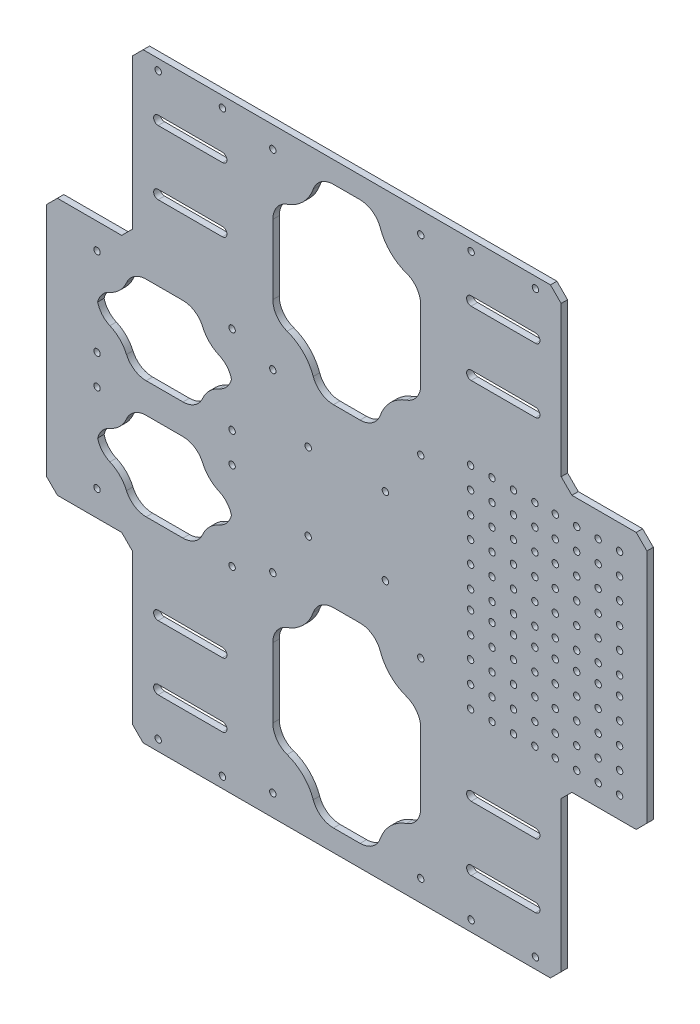
SolidWorks part; units mm, degrees
ref_plane "前视基准面" through (0, 0, 0) normal (0, 0, 1) x (1, 0, 0)
ref_plane "上视基准面" through (0, 0, 0) normal (0, 1, 0) x (1, 0, 0)
ref_plane "右视基准面" through (0, 0, 0) normal (1, 0, 0) x (0, 0, -1)
other "Configuration Table"
sketch "草图1" plane through (0, 0, 0) normal (0, 0, 1) x (1, 0, 0)
  line L0 (-100, -140) -> (-100, -60)
  line L1 (-100, 140) -> (100, 140)
  line L2 (-140, 60) -> (-140, -60)
  line L3 (-100, -140) -> (100, -140)
  line L4 (140, 60) -> (140, -60)
  line L5 (-100, 60) -> (100, -60) construction
  line L6 (-100, -60) -> (100, 60) construction
  line L7 (-100, -60) -> (-140, -60)
  line L8 (140, 60) -> (100, 60)
  line L9 (-140, 60) -> (-100, 60)
  line L10 (-100, 60) -> (-100, 140)
  line L11 (100, 60) -> (100, 140)
  line L12 (100, -140) -> (100, -60)
  line L13 (100, -60) -> (140, -60)
  line L14 (-88, -85) -> (-58, -85) construction
  line L15 (-88, -82.9) -> (-58, -82.9)
  line L16 (-88, -87.1) -> (-58, -87.1)
  line L17 (-88, -115) -> (-58, -115) construction
  line L18 (-88, -112.9) -> (-58, -112.9)
  line L19 (-88, -117.1) -> (-58, -117.1)
  line L20 (-140, 0) -> (140, 0) construction
  line L21 (0, 140) -> (0, -140) construction
  line L22 (88, -115) -> (58, -115) construction
  line L23 (88, -112.9) -> (58, -112.9)
  line L24 (88, -117.1) -> (58, -117.1)
  line L25 (88, -85) -> (58, -85) construction
  line L26 (88, -82.9) -> (58, -82.9)
  line L27 (88, -87.1) -> (58, -87.1)
  line L28 (88, 115) -> (58, 115) construction
  line L29 (88, 112.9) -> (58, 112.9)
  line L30 (88, 117.1) -> (58, 117.1)
  line L31 (88, 85) -> (58, 85) construction
  line L32 (88, 82.9) -> (58, 82.9)
  line L33 (88, 87.1) -> (58, 87.1)
  line L34 (-88, 115) -> (-58, 115) construction
  line L35 (-88, 112.9) -> (-58, 112.9)
  line L36 (-88, 117.1) -> (-58, 117.1)
  line L37 (-88, 85) -> (-58, 85) construction
  line L38 (-88, 82.9) -> (-58, 82.9)
  line L39 (-88, 87.1) -> (-58, 87.1)
  arc A0 (-88, -82.9) -> (-88, -87.1) centre (-88, -85) ccw
  arc A1 (-58, -87.1) -> (-58, -82.9) centre (-58, -85) ccw
  arc A2 (-88, -112.9) -> (-88, -117.1) centre (-88, -115) ccw
  arc A3 (-58, -117.1) -> (-58, -112.9) centre (-58, -115) ccw
  arc A4 (88, -112.9) -> (88, -117.1) centre (88, -115) cw
  arc A5 (58, -117.1) -> (58, -112.9) centre (58, -115) cw
  arc A6 (88, -82.9) -> (88, -87.1) centre (88, -85) cw
  arc A7 (58, -87.1) -> (58, -82.9) centre (58, -85) cw
  arc A8 (88, 112.9) -> (88, 117.1) centre (88, 115) ccw
  arc A9 (58, 117.1) -> (58, 112.9) centre (58, 115) ccw
  arc A10 (88, 82.9) -> (88, 87.1) centre (88, 85) ccw
  arc A11 (58, 87.1) -> (58, 82.9) centre (58, 85) ccw
  arc A12 (-88, 112.9) -> (-88, 117.1) centre (-88, 115) cw
  arc A13 (-58, 117.1) -> (-58, 112.9) centre (-58, 115) cw
  arc A14 (-88, 82.9) -> (-88, 87.1) centre (-88, 85) cw
  arc A15 (-58, 87.1) -> (-58, 82.9) centre (-58, 85) cw
  circle A16 centre (-34.5, -130) radius 1.5
  circle A17 centre (-34.5, -41) radius 1.5
  circle A18 centre (34.5, -130) radius 1.5
  circle A19 centre (34.5, -41) radius 1.5
  circle A22 centre (-34.5, 130) radius 1.5
  circle A23 centre (34.5, 130) radius 1.5
  circle A24 centre (34.5, 41) radius 1.5
  circle A25 centre (-34.5, 41) radius 1.5
  point P0 (0, 0)
  point P1 (0, 0)
  point P6 (-73, -85)
  point P23 (-73, -115)
  point P35 (73, -115)
  point P42 (73, -85)
  point P49 (73, 115)
  point P56 (73, 85)
  point P63 (-73, 115)
  point P70 (-73, 85)
  dimension "D3" = 40
  dimension "D12" = 2.1
  dimension "D13" = 2.1
  dimension "D16" = 34.5
  dimension "D17" = 89
  dimension "D20" = 3
  dimension "D21" = 3
  dimension "D1" = 280
  dimension "D2" = 40
  dimension "D4" = 280
  dimension "D5" = 80
  dimension "D6" = 80
  dimension "D7" = 80
  dimension "D8" = 30
  dimension "D9" = 25
  dimension "D10" = 30
  dimension "D11" = 30
  dimension "D14" = 12
  dimension "D15" = 12
  dimension "D18" = 10
  dimension "D19" = 34.5
extrude "凸台-拉伸1" add sketch "草图1" along normal blind 3
chamfer "倒角1" distance 5 angle 45 12 edges at (100, 60, 1.5) (100, -60, 1.5) (-100, -60, 1.5) (-100, 60, 1.5) (140, 60, 1.5) (140, -60, 1.5) (-140, -60, 1.5) (-140, 60, 1.5) (100, 140, 1.5) (-100, 140, 1.5) (-100, -140, 1.5) (100, -140, 1.5)
sketch "草图3" plane through (0, 0, 3) normal (0, 0, 1) x (1, 0, 0)
  line L0 (-140, 0) -> (140, 0) construction
  line L1 (-140, 55) -> (-140, -55) construction
  line L2 (140, -55) -> (140, 55) construction
  line L3 (0, 140) -> (0, -140) construction
  line L4 (95, 140) -> (-95, 140) construction
  line L5 (-95, -140) -> (95, -140) construction
  line L6 (-14.5, 130) -> (14.5, 130)
  line L11 (-18, 18) -> (18, -18) construction
  line L12 (-18, -18) -> (18, 18) construction
  line L17 (-34.5, 110) -> (-34.5, 61)
  line L18 (-14.5, 41) -> (14.5, 41)
  line L19 (34.5, 110) -> (34.5, 61)
  line L20 (-14.5, -41) -> (14.5, -41)
  line L21 (34.5, -110) -> (34.5, -61)
  line L22 (-14.5, -130) -> (14.5, -130)
  line L23 (-34.5, -110) -> (-34.5, -61)
  line L24 (-101.5, -48) -> (-68.5, -48)
  line L26 (-116.5, -33) -> (-116.5, -22)
  line L30 (-101.5, -7) -> (-68.5, -7)
  line L31 (-53.5, -33) -> (-53.5, -22)
  line L33 (-101.5, 7) -> (-68.5, 7)
  line L34 (-103.9279, 15.1818) -> (-66.0721, 39.8182) construction
  line L36 (-116.5, 33) -> (-116.5, 22)
  line L37 (-103.9279, 39.8182) -> (-66.0721, 15.1818) construction
  line L38 (-101.5, 48) -> (-68.5, 48)
  line L41 (-53.5, 33) -> (-53.5, 22)
  circle A0 centre (-88, 135) radius 1.5
  circle A1 centre (-58, 135) radius 1.5
  circle A42 centre (58, 135) radius 1.5
  circle A43 centre (88, 135) radius 1.5
  circle A84 centre (88, -135) radius 1.5
  circle A85 centre (58, -135) radius 1.5
  circle A86 centre (-58, -135) radius 1.5
  circle A87 centre (-88, -135) radius 1.5
  circle A92 centre (-18, 18) radius 1.5
  circle A93 centre (18, 18) radius 1.5
  circle A94 centre (18, -18) radius 1.5
  circle A95 centre (-18, -18) radius 1.5
  arc A240 (-14.5, 41) -> (-34.5, 61) centre (-34.5, 41) ccw
  arc A241 (34.5, 61) -> (14.5, 41) centre (34.5, 41) ccw
  arc A242 (-34.5, 110) -> (-14.5, 130) centre (-34.5, 130) ccw
  arc A243 (14.5, 130) -> (34.5, 110) centre (34.5, 130) ccw
  arc A244 (34.5, -61) -> (14.5, -41) centre (34.5, -41) cw
  arc A245 (14.5, -130) -> (34.5, -110) centre (34.5, -130) cw
  arc A246 (-34.5, -110) -> (-14.5, -130) centre (-34.5, -130) cw
  arc A247 (-14.5, -41) -> (-34.5, -61) centre (-34.5, -41) cw
  circle A262 centre (-116.5, 48) radius 1.5
  circle A263 centre (-53.5, 48) radius 1.5
  circle A321 centre (-53.5, 7) radius 1.5
  circle A322 centre (-116.5, 7) radius 1.5
  arc A323 (-116.5, 33) -> (-101.5, 48) centre (-116.5, 48) ccw
  arc A324 (-68.5, 48) -> (-53.5, 33) centre (-53.5, 48) ccw
  arc A325 (-101.5, 7) -> (-116.5, 22) centre (-116.5, 7) ccw
  arc A326 (-53.5, 22) -> (-68.5, 7) centre (-53.5, 7) ccw
  circle A327 centre (-53.5, -7) radius 1.5
  circle A328 centre (-53.5, -48) radius 1.5
  circle A329 centre (-116.5, -48) radius 1.5
  circle A330 centre (-116.5, -7) radius 1.5
  arc A331 (-116.5, -33) -> (-101.5, -48) centre (-116.5, -48) cw
  arc A357 (-101.5, -7) -> (-116.5, -22) centre (-116.5, -7) cw
  arc A358 (-53.5, -22) -> (-68.5, -7) centre (-53.5, -7) cw
  arc A359 (-68.5, -48) -> (-53.5, -33) centre (-53.5, -48) cw
  point P2 (0, 0)
  point P29 (-85, 27.5)
  point P189 (0, 0)
  point P194 (0, 0)
  dimension "D1" = 55
  dimension "D4" = 63
  dimension "D5" = 41
extrude "切除-拉伸2" cut sketch "草图3" against normal blind 10
fillet "圆角1" radius 10 32 edges at (-34.5, -61, 1.5) (-14.5, -41, 1.5) (34.5, -61, 1.5) (14.5, -41, 1.5) (14.5, -130, 1.5) (34.5, -110, 1.5) (-14.5, -130, 1.5) (-34.5, -110, 1.5) (-34.5, 61, 1.5) (-14.5, 41, 1.5) (14.5, 41, 1.5) (34.5, 61, 1.5) (34.5, 110, 1.5) (14.5, 130, 1.5) (-34.5, 110, 1.5) (-14.5, 130, 1.5) (-68.5, -7, 1.5) (-101.5, -7, 1.5) (-116.5, -22, 1.5) (-116.5, -33, 1.5) (-101.5, -48, 1.5) (-68.5, -48, 1.5) (-53.5, -33, 1.5) (-53.5, -22, 1.5) (-53.5, 22, 1.5) (-53.5, 33, 1.5) (-68.5, 48, 1.5) (-68.5, 7, 1.5) (-101.5, 7, 1.5) (-116.5, 22, 1.5) (-116.5, 33, 1.5) (-101.5, 48, 1.5)
sketch "草图4" plane through (0, 0, 3) normal (0, 0, 1) x (1, 0, 0)
  circle A4 centre (57.75, 48.5) radius 1.5
  circle A5 centre (57.75, -10) radius 1.5
  circle A6 centre (67.75, 48.5) radius 1.5
  circle A7 centre (67.75, -10) radius 1.5
  circle A10 centre (77.75, 48.5) radius 1.5
  circle A11 centre (77.75, -10) radius 1.5
  circle A12 centre (87.75, 48.5) radius 1.5
  circle A13 centre (87.75, -10) radius 1.5
  circle A14 centre (57.75, 38.5) radius 1.5
  circle A15 centre (67.75, 38.5) radius 1.5
  circle A16 centre (77.75, 38.5) radius 1.5
  circle A17 centre (87.75, 38.5) radius 1.5
  circle A18 centre (57.75, 28.5) radius 1.5
  circle A19 centre (67.75, 28.5) radius 1.5
  circle A20 centre (77.75, 28.5) radius 1.5
  circle A21 centre (87.75, 28.5) radius 1.5
  circle A22 centre (57.75, 18.5) radius 1.5
  circle A23 centre (67.75, 18.5) radius 1.5
  circle A24 centre (77.75, 18.5) radius 1.5
  circle A25 centre (87.75, 18.5) radius 1.5
  circle A26 centre (57.75, 8.5) radius 1.5
  circle A27 centre (67.75, 8.5) radius 1.5
  circle A28 centre (77.75, 8.5) radius 1.5
  circle A29 centre (87.75, 8.5) radius 1.5
  circle A30 centre (57.75, -1.5) radius 1.5
  circle A31 centre (67.75, -1.5) radius 1.5
  circle A32 centre (77.75, -1.5) radius 1.5
  circle A33 centre (87.75, -1.5) radius 1.5
  circle A34 centre (57.75, -20) radius 1.5
  circle A35 centre (67.75, -20) radius 1.5
  circle A36 centre (77.75, -20) radius 1.5
  circle A37 centre (87.75, -20) radius 1.5
  circle A38 centre (57.75, -30) radius 1.5
  circle A39 centre (67.75, -30) radius 1.5
  circle A40 centre (77.75, -30) radius 1.5
  circle A41 centre (87.75, -30) radius 1.5
  circle A42 centre (57.75, -40) radius 1.5
  circle A43 centre (67.75, -40) radius 1.5
  circle A44 centre (77.75, -40) radius 1.5
  circle A45 centre (87.75, -40) radius 1.5
  circle A46 centre (57.75, -50) radius 1.5
  circle A47 centre (67.75, -50) radius 1.5
  circle A48 centre (77.75, -50) radius 1.5
  circle A49 centre (87.75, -50) radius 1.5
  circle A50 centre (97.25, -50) radius 1.5
  circle A51 centre (107.25, -50) radius 1.5
  circle A52 centre (117.25, -50) radius 1.5
  circle A53 centre (127.25, -50) radius 1.5
  circle A54 centre (127.25, -40) radius 1.5
  circle A55 centre (117.25, -40) radius 1.5
  circle A56 centre (107.25, -40) radius 1.5
  circle A57 centre (97.25, -40) radius 1.5
  circle A58 centre (97.25, -30) radius 1.5
  circle A59 centre (107.25, -30) radius 1.5
  circle A60 centre (117.25, -30) radius 1.5
  circle A61 centre (127.25, -30) radius 1.5
  circle A62 centre (127.25, -20) radius 1.5
  circle A63 centre (117.25, -20) radius 1.5
  circle A64 centre (107.25, -20) radius 1.5
  circle A65 centre (97.25, -20) radius 1.5
  circle A66 centre (97.25, -10) radius 1.5
  circle A67 centre (107.25, -10) radius 1.5
  circle A68 centre (117.25, -10) radius 1.5
  circle A69 centre (127.25, -10) radius 1.5
  circle A70 centre (127.25, -1.5) radius 1.5
  circle A71 centre (117.25, -1.5) radius 1.5
  circle A72 centre (107.25, -1.5) radius 1.5
  circle A73 centre (97.25, -1.5) radius 1.5
  circle A74 centre (97.25, 8.5) radius 1.5
  circle A75 centre (107.25, 8.5) radius 1.5
  circle A76 centre (117.25, 8.5) radius 1.5
  circle A77 centre (127.25, 8.5) radius 1.5
  circle A78 centre (127.25, 18.5) radius 1.5
  circle A79 centre (117.25, 18.5) radius 1.5
  circle A80 centre (107.25, 18.5) radius 1.5
  circle A81 centre (97.25, 18.5) radius 1.5
  circle A82 centre (97.25, 28.5) radius 1.5
  circle A83 centre (107.25, 28.5) radius 1.5
  circle A84 centre (117.25, 28.5) radius 1.5
  circle A85 centre (127.25, 28.5) radius 1.5
  circle A86 centre (127.25, 38.5) radius 1.5
  circle A87 centre (117.25, 38.5) radius 1.5
  circle A88 centre (107.25, 38.5) radius 1.5
  circle A89 centre (97.25, 38.5) radius 1.5
  circle A90 centre (97.25, 48.5) radius 1.5
  circle A91 centre (107.25, 48.5) radius 1.5
  circle A92 centre (117.25, 48.5) radius 1.5
  circle A93 centre (127.25, 48.5) radius 1.5
  dimension "D3" = 6
  dimension "D4" = 5
extrude "切除-拉伸3" cut sketch "草图4" against normal blind 10
